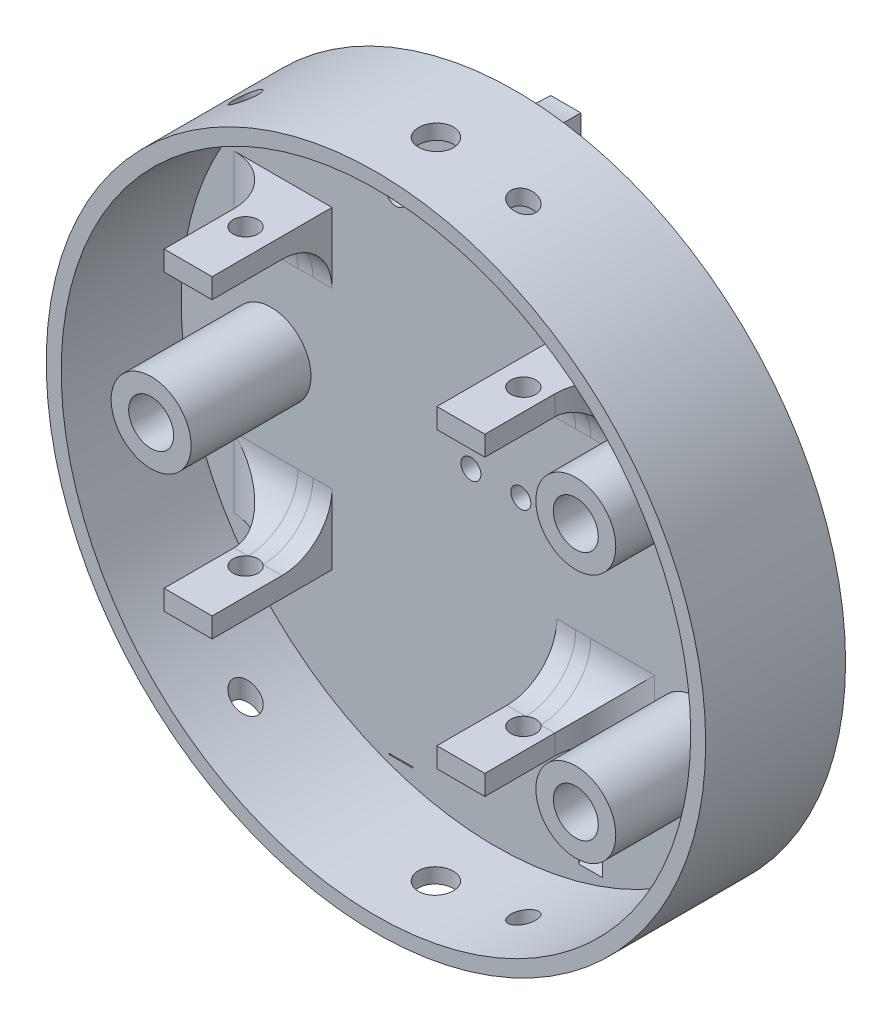
SolidWorks part; units mm, degrees
ref_plane "Alzado" through (0, 0, 0) normal (0, 0, 1) x (1, 0, 0)
ref_plane "Planta" through (0, 0, 0) normal (0, 1, 0) x (1, 0, 0)
ref_plane "Vista lateral" through (0, 0, 0) normal (1, 0, 0) x (0, 0, -1)
sketch "Croquis1" plane through (0, 0, 0) normal (0, 0, 1) x (1, 0, 0)
  line L0 (10, 20) -> (-10, 20) construction
  circle A0 centre (0, 0) radius 33
  circle A1 centre (-2.5, 0) radius 1
  circle A2 centre (2.5, 0) radius 1
  circle A3 centre (0, 20) radius 1
  circle A4 centre (10, 20) radius 1
  circle A5 centre (-10, 20) radius 1
  point P9 (0, 20)
  dimension "D1" = 66
  dimension "D4" = 2
  dimension "D7" = 2
  dimension "D2" = 2.5
  dimension "D3" = 2.5
  dimension "D5" = 20
  dimension "D6" = 20
extrude "Saliente-Extruir1" add sketch "Croquis1" along normal blind 2
sketch "Croquis2" plane through (0, 0, 2) normal (0, 0, 1) x (1, 0, 0)
  line L0 (-21.2, -15.7) -> (-16.4, -15.7)
  line L1 (10.9, -15.7) -> (6.1, -15.7)
  line L2 (-21.2, -15.7) -> (-21.2, -13.7)
  line L3 (-21.2, -13.7) -> (-16.4, -13.7)
  line L4 (-16.4, -13.7) -> (-16.4, -15.7)
  line L5 (6.1, -15.7) -> (6.1, -13.7)
  line L6 (6.1, -13.7) -> (10.9, -13.7)
  line L7 (10.9, -13.7) -> (10.9, -15.7)
  line L8 (6.1, -15.7) -> (10.9, -15.7)
  line L9 (0, 0) -> (12.8027, 0) construction
  line L10 (10.9, 13.7) -> (10.9, 15.7)
  line L11 (10.9, 15.7) -> (6.1, 15.7)
  line L12 (6.1, 13.7) -> (10.9, 13.7)
  line L13 (6.1, 15.7) -> (6.1, 13.7)
  line L14 (-16.4, 13.7) -> (-16.4, 15.7)
  line L15 (-21.2, 15.7) -> (-16.4, 15.7)
  line L16 (-21.2, 15.7) -> (-21.2, 13.7)
  line L17 (-21.2, 13.7) -> (-16.4, 13.7)
  point P2 (0, -15.7)
  point P3 (-16.4, -15.7)
  point P13 (8.5, -15.7)
  point P16 (8.5, 15.7)
  dimension "D1" = 32.1
  dimension "D2" = 10.9
  dimension "D3" = 15.7
  dimension "D4" = 4.8
  dimension "D5" = 4.8
  dimension "D6" = 2
  dimension "D7" = 2
extrude "Saliente-Extruir2" add sketch "Croquis2" along normal blind 12 contours L7 L6 L5 L1 | L4 L3 L2 L0 | L16 L17 L14 L15 | L11 L13 L12 L10 region at (-18.8, -14.7, 2) region at (8.5, -14.7, 2) region at (8.5, 14.7, 2) region at (-18.8, 14.7, 2)
sketch "Croquis3" plane through (0, -15.7, 0) normal (0, -1, 0) x (1, 0, 0)
  line L0 (-21.2, 14) -> (-21.2, 2) construction
  line L3 (10.9, 14) -> (10.9, 2) construction
  line L6 (-21.2, 2) -> (-16.4, 2) construction
  circle A0 centre (-19.05, 8) radius 1.25
  circle A1 centre (8.75, 8) radius 1.25
  dimension "D1" = 2.5
  dimension "D2" = 2.15
  dimension "D3" = 2.15
  dimension "D4" = 6
extrude "Cortar-Extruir1" cut sketch "Croquis3" against normal up to surface (31.4 mm away) up to face at (8.5, 15.7, 8)
ref_plane "Plano1" through (0, -33, 0) normal (0, -1, 0) x (-1, 0, 0)
ref_plane "Plano2" through (0, -28.85, 0) normal (0, -1, 0) x (-1, 0, 0)
sketch "Croquis5" plane through (0, -28.85, 0) normal (0, -1, 0) x (-1, 0, 0)
  line L0 (-8.75, -8) -> (19.05, -8) construction
  line L1 (0, 0) -> (0, -8) construction
  line L2 (-33, -2) -> (33, -2) construction
  line L3 (-10.68, -2) -> (-8.3104, -2)
  line L4 (33, 0) -> (-33, 0) construction
  line L5 (9.277, 0) -> (6.408, 0)
  line L6 (8.3104, -2) -> (10.68, -2)
  line L7 (-6.408, 0) -> (-9.277, 0)
  arc A0 (-9.277, 0) -> (-10.68, -2) centre (0, -8) ccw
  arc A1 (-6.408, 0) -> (-8.3104, -2) centre (0, -8) ccw
  arc A2 (10.68, -2) -> (9.277, 0) centre (0, -8) ccw
  arc A3 (8.3104, -2) -> (6.408, 0) centre (0, -8) ccw
  dimension "D1" = 24.5
  dimension "D2" = 20.5
extrude "Cortar-Extruir3" cut sketch "Croquis5" against normal blind 2
mirror "Simetría1" about plane through (0, 0, 0) normal (0, 1, 0) of "Cortar-Extruir3"
sketch "Croquis6" plane through (0, 0, 0) normal (0, 0, -1) x (-1, 0, 0)
  circle A0 centre (-20, 12.5) radius 2.25
  circle A1 centre (-20, -12.5) radius 2.25
  circle A2 centre (22.5, 0) radius 2.25
  dimension "D1" = 4.5
  dimension "D2" = 4.5
  dimension "D3" = 4.5
  dimension "D6" = 25
  dimension "D7" = 12.5
  dimension "D4" = 22.5
  dimension "D5" = 20
extrude "Cortar-Extruir4" cut sketch "Croquis6" against normal blind 2.5
sketch "Croquis7" plane through (0, 0, 2) normal (0, 0, 1) x (1, 0, 0)
  circle A2 centre (0, 0) radius 33 construction
  circle A9 centre (0, 0) radius 33
  circle A11 centre (0, 0) radius 31.5
  dimension "D1" = 1.5
extrude "Saliente-Extruir3" add sketch "Croquis7" along normal blind 12
ref_plane "Plano3" through (0, -33, 0) normal (0, -1, 0) x (-1, 0, 0)
sketch "Croquis8" plane through (0, -33, 0) normal (0, -1, 0) x (-1, 0, 0)
  circle A0 centre (-8.75, -8) radius 1.25 construction
  circle A1 centre (-8.75, -8) radius 1.25
  circle A2 centre (19.05, -8) radius 1.25 construction
  circle A3 centre (19.05, -8) radius 1.25
  circle A4 centre (0, -8) radius 1.75
  dimension "D1" = 3.5
extrude "Cortar-Extruir5" cut sketch "Croquis8" against normal blind 70
sketch "Sketch1" plane through (0, 0, 0) normal (0, 0, -1) x (-1, 0, 0)
  line L0 (6.408, 26.85) -> (6.408, 28.85) construction
  line L1 (-1.502, 29.35) -> (1.498, 29.35)
  line L2 (-1.502, 29.35) -> (-1.502, 26.35)
  line L3 (-1.502, 26.35) -> (1.498, 26.35)
  line L4 (1.498, 29.35) -> (1.498, 26.35)
  line L5 (-1.502, 29.35) -> (1.498, 26.35) construction
  line L6 (-1.502, 26.35) -> (1.498, 29.35) construction
  line L7 (0, 0) -> (-11.4103, 0) construction
  line L8 (-1.502, -26.35) -> (1.498, -29.35) construction
  line L9 (-1.502, -29.35) -> (1.498, -26.35) construction
  line L10 (1.498, -29.35) -> (1.498, -26.35)
  line L11 (-1.502, -26.35) -> (1.498, -26.35)
  line L12 (-1.502, -29.35) -> (-1.502, -26.35)
  line L13 (-1.502, -29.35) -> (1.498, -29.35)
  line L14 (-6.408, -26.85) -> (-6.408, -28.85) construction
  point P0 (-0.002, 27.85)
  point P8 (6.408, 27.85)
  point P15 (-0.002, -27.85)
  dimension "D1" = 4.91
  dimension "D2" = 3
  dimension "D3" = 3
  dimension "D4" = 4.906
extrude "Boss-Extrude1" add sketch "Sketch1" along normal blind 5
fillet "Fillet1" radius 2 6 edges at (1.502, 27.85, 0) (-1.498, -27.85, 0) (0.002, 26.35, 0) (0.002, 29.35, 0) (0.002, -26.35, 0) (0.002, -29.35, 0) second distance 5 first distance on face at (0.002, 27.85, 0)
sketch "Sketch2" plane through (0, 0, 2) normal (0, 0, 1) x (1, 0, 0)
  line L1 (-10.68, -26.85) -> (-5.6668, -26.85)
  line L2 (-10.68, -26.85) -> (-10.68, -28.75)
  line L3 (-10.68, -28.75) -> (-5.6668, -28.75)
  line L4 (-5.6668, -26.85) -> (-5.6668, -28.75)
  line L5 (10.68, 26.85) -> (5.4941, 26.85)
  line L6 (10.68, 26.85) -> (10.68, 28.75)
  line L7 (10.68, 28.75) -> (5.4941, 28.75)
  line L8 (5.4941, 26.85) -> (5.4941, 28.75)
extrude "Tapon" add sketch "Sketch2" against normal up to surface (2 mm away) up to face at (1.002, 26.1, 0)
fillet "Fillet4" radius 5 8 edges at (-21.2, 14.7, 2) (-21.2, -14.7, 2) (-18.8, -13.7, 2) (-18.8, 13.7, 2) (10.9, 14.7, 2) (8.5, 13.7, 2) (8.5, -13.7, 2) (10.9, -14.7, 2)
sketch "Croquis9" plane through (0, 0, 2) normal (0, 0, 1) x (1, 0, 0)
  circle A0 centre (20, -12.5) radius 2.25 construction
  circle A1 centre (20, -12.5) radius 2.25
  circle A2 centre (-22.5, 0) radius 2.25 construction
  circle A3 centre (-22.5, 0) radius 2.25
  circle A4 centre (20, 12.5) radius 2.25 construction
  circle A5 centre (20, 12.5) radius 2.25
  circle A6 centre (-22.5, 0) radius 4
  circle A7 centre (20, -12.5) radius 4
  circle A8 centre (20, 12.5) radius 4
  dimension "D1" = 8
extrude "Saliente-Extruir4" add sketch "Croquis9" along normal up to surface (12 mm away) up to face at (33, 0, 14)
equation "\"D2@Croquis6\"=\"D1@Croquis6\""
equation "\"D3@Croquis6\"=\"D1@Croquis6\""
equation "\"D7@Croquis6\"=\"D6@Croquis6\"/2"
